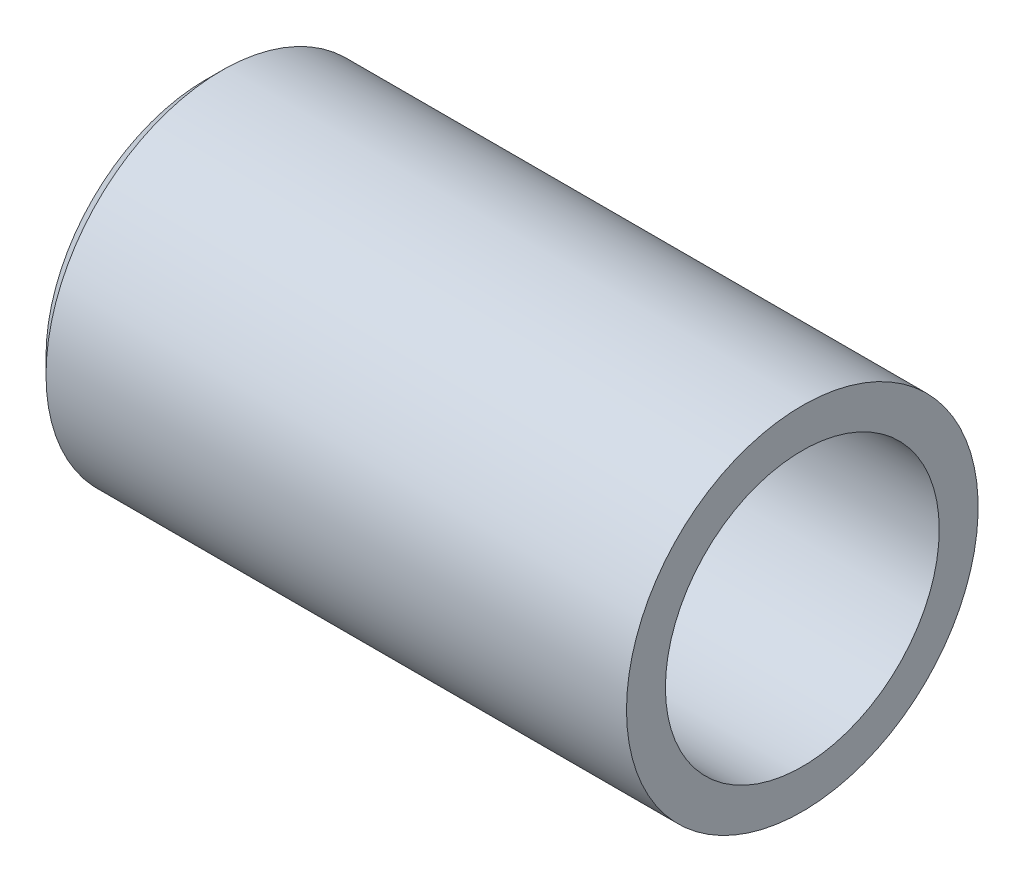
SolidWorks part; units mm, degrees
material "Nylon 6/10"
ref_plane "Front Plane" through (0, 0, 0) normal (0, 0, 1) x (1, 0, 0)
ref_plane "Top Plane" through (0, 0, 0) normal (0, 1, 0) x (1, 0, 0)
ref_plane "Right Plane" through (0, 0, 0) normal (1, 0, 0) x (0, 0, -1)
sketch "Sketch1" plane through (0, 0, 0) normal (0, 0, 1) x (1, 0, 0)
  line L0 (0, 0) -> (22.1407, 0) construction
  line L1 (6.7033, 5.4227) -> (24.6062, 5.4227)
  line L3 (6.2063, 4.2228) -> (24.6062, 4.2228)
  line L4 (24.6062, 5.4227) -> (24.6062, 4.2228)
  line L5 (24.6062, 11.1125) -> (24.6062, -11.1125) construction
  line L6 (50.5354, 3.9688) -> (-48.4378, 3.9688) construction
  line L7 (6.2063, -4.1672) -> (6.2063, 4.1672) construction
  line L8 (6.2063, 4.2228) -> (6.2063, 4.9257)
  line L9 (6.2063, 4.9257) -> (6.7033, 5.4227)
  dimension "D4" = 45
  dimension "D2" = 1.2
  dimension "D1" = 0.254
revolve "Revolve1" add sketch "Sketch1" angle 360 about L0
equation "\"D2@Sketch1\"=1.2mm"
